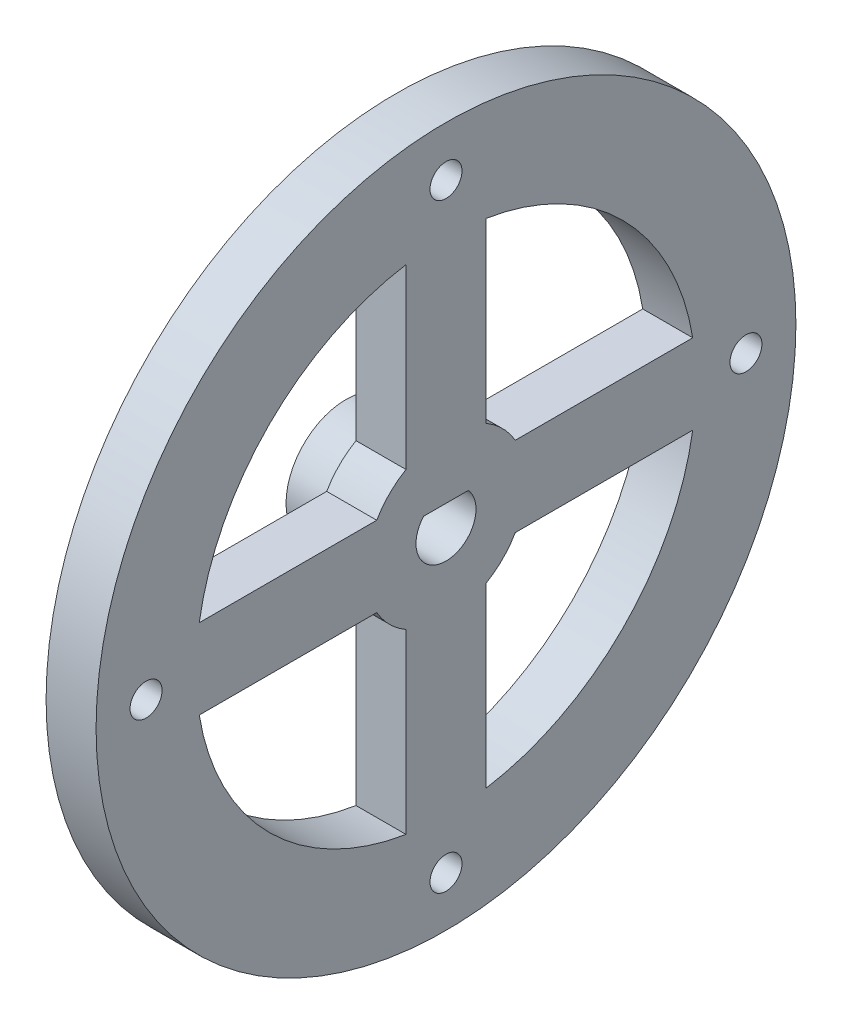
SolidWorks part; units mm, degrees
ref_plane "Front Plane" through (0, 0, 0) normal (0, 0, 1) x (1, 0, 0)
ref_plane "Top Plane" through (0, 0, 0) normal (0, 1, 0) x (1, 0, 0)
ref_plane "Right Plane" through (0, 0, 0) normal (1, 0, 0) x (0, 0, -1)
sketch "Sketch1" plane through (0, 0, 0) normal (1, 0, 0) x (0, 0, -1)
  line L0 (0, 0) -> (0, 50000) construction
  line L1 (4, 6.9282) -> (4, 24.6779)
  line L2 (-4, 24.6779) -> (-4, 6.9282)
  line L3 (-24.6779, -4) -> (-6.9282, -4)
  line L4 (-6.9282, 4) -> (-24.6779, 4)
  line L5 (4, -24.6779) -> (4, -6.9282)
  line L6 (-4, -6.9282) -> (-4, -24.6779)
  line L7 (24.6779, 4) -> (6.9282, 4)
  line L8 (6.9282, -4) -> (24.6779, -4)
  line L9 (-2.2361, 2) -> (2.2361, 2)
  circle A0 centre (0, 0) radius 35
  arc A1 (-2.2361, 2) -> (2.2361, 2) centre (0, 0) ccw
  arc A2 (-6.9282, -4) -> (-4, -6.9282) centre (0, 0) ccw
  arc A3 (-24.6779, -4) -> (-4, -24.6779) centre (0, 0) ccw
  arc A4 (-4, 6.9282) -> (-6.9282, 4) centre (0, 0) ccw
  arc A5 (24.6779, 4) -> (4, 24.6779) centre (0, 0) ccw
  arc A6 (4, -24.6779) -> (24.6779, -4) centre (0, 0) ccw
  arc A7 (4, -6.9282) -> (6.9282, -4) centre (0, 0) ccw
  arc A8 (6.9282, 4) -> (4, 6.9282) centre (0, 0) ccw
  arc A9 (-24.6779, 4) -> (-4, 24.6779) centre (0, 0) cw
  point P27 (0, 0)
  dimension "D1" = 70
  dimension "D2" = 6
  dimension "D5" = 16
  dimension "D6" = 50
  dimension "D3" = 8
  dimension "D7" = 2
  dimension "D4" = 4
extrude "Boss-Extrude1" add sketch "Sketch1" along normal blind 5
sketch "Sketch2" plane through (0, 0, 0) normal (-1, 0, 0) x (0, 0, 1)
  circle A0 centre (0, 0) radius 30 construction
  circle A1 centre (0, 30) radius 1.6
  circle A2 centre (30, 0) radius 1.6
  circle A3 centre (0, -30) radius 1.6
  circle A4 centre (-30, 0) radius 1.6
  point P14 (0, 0)
  dimension "D1" = 60
  dimension "D2" = 3.2
  dimension "D3" = 4
extrude "Cut-Extrude1" cut sketch "Sketch2" against normal through all
sketch "Sketch3" plane through (0, 0, 0) normal (-1, 0, 0) x (0, 0, 1)
  line L0 (-2.2361, 2) -> (2.2361, 2) construction
  line L1 (-2.2361, 2) -> (2.2361, 2)
  circle A2 centre (0, 0) radius 6
  arc A3 (-2.2361, 2) -> (2.2361, 2) centre (0, 0) ccw construction
  arc A4 (-2.2361, 2) -> (2.2361, 2) centre (0, 0) ccw
  dimension "D1" = 12
extrude "Boss-Extrude2" add sketch "Sketch3" along normal blind 5
sketch "Sketch6" plane through (0, 0, 0) normal (-1, 0, 0) x (0, 0, 1)
  circle A0 centre (0, 30) radius 3
  circle A1 centre (30, 0) radius 3
  circle A2 centre (0, -30) radius 3
  circle A3 centre (-30, 0) radius 3
  point P12 (0, 0)
  dimension "D1" = 6
  dimension "D2" = 4
extrude "Cut-Extrude2" cut sketch "Sketch6" against normal blind 2
